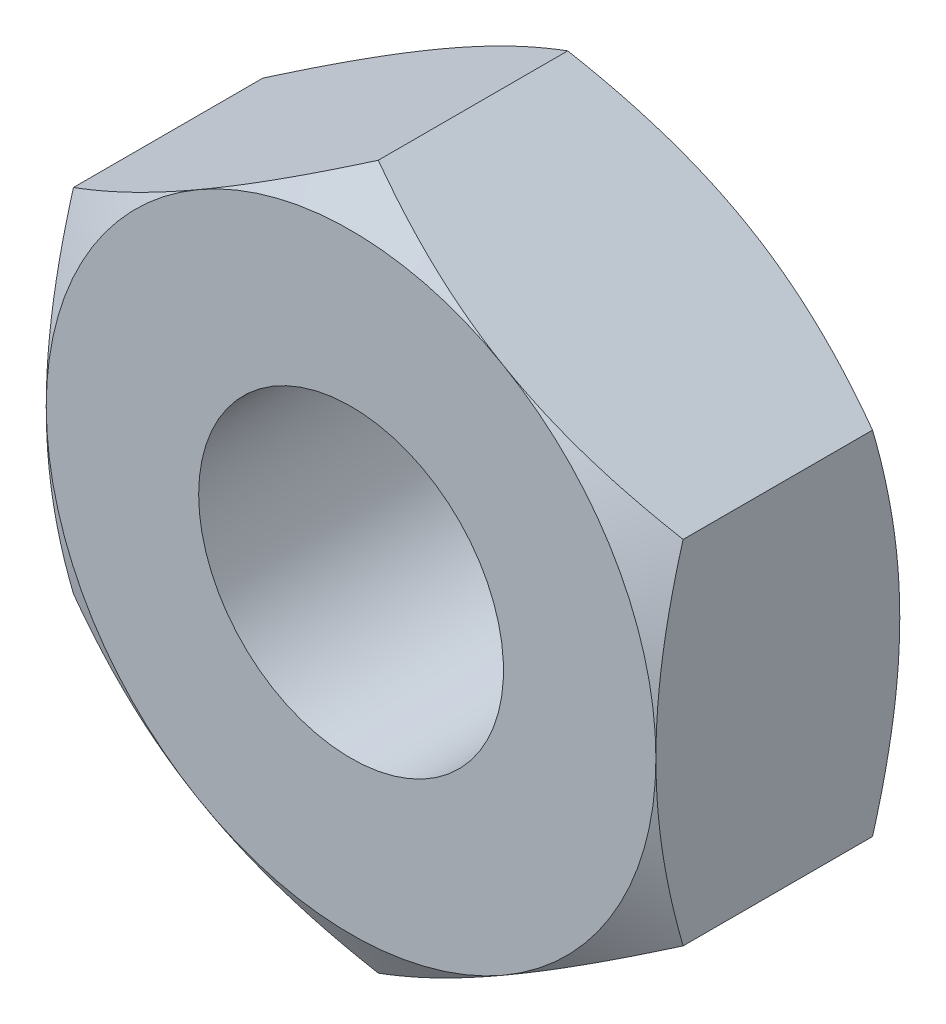
SolidWorks part; units mm, degrees
ref_plane "Front" through (0, 0, 0) normal (0, 0, 1) x (1, 0, 0)
ref_plane "Top" through (0, 0, 0) normal (0, 1, 0) x (1, 0, 0)
ref_plane "Right" through (0, 0, 0) normal (1, 0, 0) x (0, 0, -1)
sketch "Sketch1" plane through (0, 0, 0) normal (0, 0, 1) x (1, 0, 0)
  line L1 (-2.5, 1.4434) -> (-2.5, -1.4434)
  line L2 (-2.5, -1.4434) -> (0, -2.8868)
  line L3 (0, -2.8868) -> (2.5, -1.4434)
  line L4 (2.5, -1.4434) -> (2.5, 1.4434)
  line L5 (2.5, 1.4434) -> (0, 2.8868)
  line L6 (0, 2.8868) -> (-2.5, 1.4434)
  circle A0 centre (0, 0) radius 2.5 construction
  circle A1 centre (0, 0) radius 1.25 construction
  point P10 (0, 1.25)
  dimension "hex" = 5
  dimension "dia" = 2.5
extrude "Extrude1" add sketch "Sketch1" along normal mid plane 2
sketch "Sketch4" plane through (0, 0, -1) normal (0, 0, -1) x (-1, 0, 0)
  circle A0 centre (0, 0) radius 1.25 construction
  circle A1 centre (0, 0) radius 1.25
sketch "Sketch10" plane through (0, 0, 1) normal (0, 0, 1) x (1, 0, 0)
  circle A0 centre (0, 0) radius 1.25 construction
  circle A1 centre (0, 0) radius 1.25
extrude "Cut-Extrude2" cut sketch "Sketch10" against normal through all draft 45
sketch "Sketch11" plane through (0, 0, -1) normal (0, 0, -1) x (-1, 0, 0)
  circle A0 centre (0, 0) radius 1.25 construction
  circle A1 centre (0, 0) radius 1.25
extrude "Cut-Extrude3" cut sketch "Sketch11" against normal through all draft 45
sketch "Sketch13" plane through (0, 0, -1) normal (0, 0, -1) x (-1, 0, 0)
  circle A0 centre (0, 0) radius 1.25 construction
  circle A1 centre (0, 0) radius 1.25
extrude "Boss-Extrude1" add sketch "Sketch13" against normal up to vertex separate body up to point (0, -2.5, 1.4434)
curve "Helix/Spiral3" [suppressed] pitch 0.45 height 2 turns 4.4444
sketch "Sketch12" plane through (0, 0, 0) normal (1, 0, 0) x (0, 0, -1)
  line L0 (1.3938, 1.25) -> (1, 1.25)
  line L1 (1.3938, 1.25) -> (1.225, 0.9577)
  line L2 (1.225, 0.9577) -> (1.1688, 0.9577)
  line L3 (1.1688, 0.9577) -> (1, 1.25)
  line L4 (1.1969, 0.9577) -> (1.1969, 1.25) construction
  line L5 (1.0844, 1.1039) -> (1.3094, 1.1039) construction
  dimension "D1" = 60
  dimension "D2" = 0.0563
  dimension "D3" = 0.225
sweep "Cut-Sweep1" [suppressed] cut profiles "Sketch12" path "Helix/Spiral3"
combine bodies "Combine1" operation type subtract main body 116 bodies to subtract 117
sketch "Sketch7" plane through (0, 0, 1) normal (0, 0, 1) x (1, 0, 0)
  circle A0 centre (0, 0) radius 2.5 construction
  circle A1 centre (0, 0) radius 2.5
extrude "Extrude2" cut sketch "Sketch7" against normal blind 25.4 draft 60 flip side to cut
mirror "Mirror2" about plane through (0, 0, 0) normal (0, 0, 1) of "Extrude2"
sketch "Sketch8" plane through (0, 0, 1) normal (0, 0, 1) x (1, 0, 0)
  line L0 (-0.8839, 0.8839) -> (0, 0) construction
  line L1 (0, -1.2361) -> (0, 1.2361) construction
  circle A1 centre (0, 0) radius 1.25 construction
  point P0 (-0.8839, 0.8839)
  dimension "D1" = 45
sketch "Sketch14" plane through (0, 0, 1) normal (0, 0, 1) x (1, 0, 0)
  line L0 (0, 0) -> (-1.25, 0) construction
  circle A0 centre (0, 0) radius 1.25 construction
sketch "Sketch15" plane through (0, 0, 0) normal (1, 0, 0) x (0, 0, -1)
  line L0 (1, -1.25) -> (1, 1.25) construction
  line L1 (-1, 1.25) -> (-1, -1.25) construction
  point P0 (-1, 0)
  point P1 (1, 0)
equation "\"D3@Helix/Spiral3\" = \"length@Extrude1\" "
equation "\"D2@Sketch12\" = \"D4@Helix/Spiral3\"*.125"
equation "\"D3@Sketch12\" = \"D4@Helix/Spiral3\"*.50"
